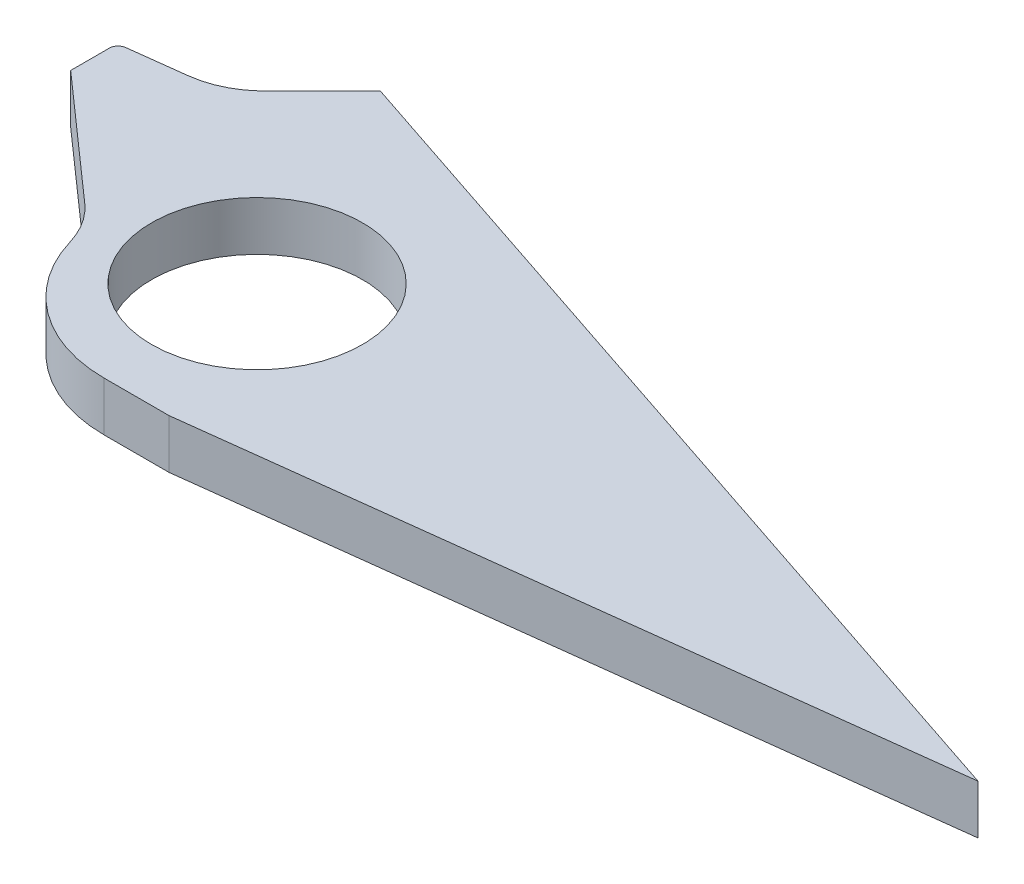
SolidWorks part; units mm, degrees
material "Plain Carbon Steel"
ref_plane "Front Plane" through (0, 0, 0) normal (0, 0, 1) x (1, 0, 0)
ref_plane "Top Plane" through (0, 0, 0) normal (0, 1, 0) x (1, 0, 0)
ref_plane "Right Plane" through (0, 0, 0) normal (1, 0, 0) x (0, 0, -1)
sketch "Sketch1" plane through (0, 0, 0) normal (0, 1, 0) x (1, 0, 0)
  line L9 (-9, 10) -> (-6, 13)
  line L11 (-9, 8.7) -> (-15.8, 8.7)
  line L12 (-15.8, 8.7) -> (-15.8, 5.2)
  line L14 (-9, 10) -> (-9, 8.7)
  line L18 (4, -9) -> (-6, -9)
  line L22 (-15.8, 5.2) -> (-7.6609, -2)
  line L23 (-7.6609, -2) -> (-6, -9)
  line L24 (-6, 13) -> (45, -4)
  line L25 (45, -4) -> (4, -9)
  circle A0 centre (0, 0) radius 6
  dimension "D1" = 12
  dimension "D3" = 6
  dimension "D4" = 10
  dimension "D5" = 45
  dimension "D6" = 5
  dimension "D10" = 3
  dimension "D11" = 1.3
  dimension "D12" = 6.8
  dimension "D13" = 3.5
  dimension "D14" = 7
  dimension "D17" = 15.8
  dimension "D20" = 9
extrude "Boss-Extrude1" add sketch "Sketch1" along normal blind 2.8
chamfer "Chamfer1" distance 7 angle 7 1 edges at (-15.8, 1.4, -8.7) first distance on face at (-12.4, 1.4, -8.7)
fillet "Fillet4" radius 5 1 edges at (-9, 1.4, -8.6754)
fillet "Fillet5" radius 0.5 1 edges at (-15.8, 1.4, -7.8405)
fillet "Fillet10" radius 5 1 edges at (-7.6609, 1.4, 2)
fillet "Fillet11" radius 8 1 edges at (-6, 1.4, 9)
sketch "Sketch2" plane through (0, 2.8, 0) normal (0, 1, 0) x (1, 0, 0)
  circle A0 centre (10.6696, 0) radius 1.2022
